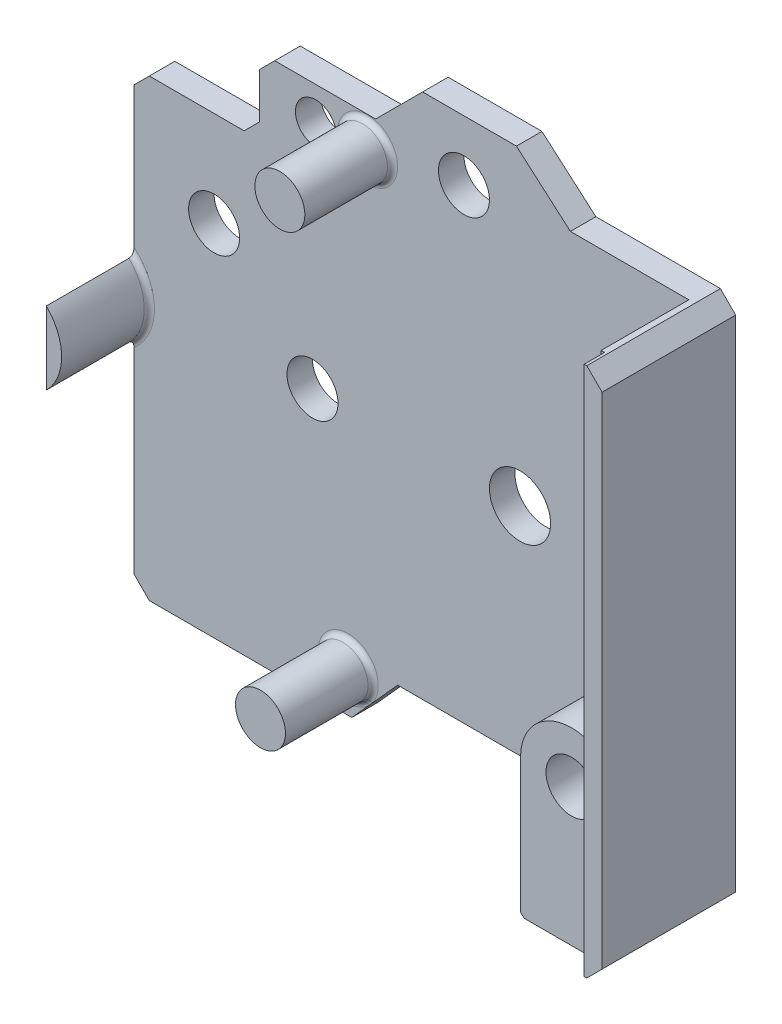
SolidWorks part; units mm, degrees
note: The reader was unsure of these and kept them because the rebuilt part matched: shared geometry of "스케치2<2>".
ref_plane "정면" through (0, 0, 0) normal (0, 0, 1) x (1, 0, 0)
ref_plane "윗면" through (0, 0, 0) normal (0, 1, 0) x (1, 0, 0)
ref_plane "우측면" through (0, 0, 0) normal (1, 0, 0) x (0, 0, -1)
sketch "스케치1" plane through (0, 0, 0) normal (0, 0, 1) x (1, 0, 0)
  line L0 (-6.6755, -27.7059) -> (-2.1735, -22.7059)
  line L1 (0.2695, 28.8941) -> (9.4695, 28.8941)
  line L2 (-42.0305, 9.3941) -> (-42.0305, -27.7059)
  line L3 (-42.0305, -27.7059) -> (-6.6755, -27.7059)
  line L4 (41.6695, 12.6741) -> (41.6695, -27.7059)
  line L5 (-2.1735, -22.7059) -> (13.2865, -22.7059)
  line L6 (13.2865, -22.7059) -> (18.8395, -27.7059)
  line L7 (18.8395, -27.7059) -> (41.6695, -27.7059)
  line L8 (-27.1305, 24.2941) -> (-42.0305, 9.3941)
  line L9 (30.0112, 24.2941) -> (41.6695, 12.6741)
  line L10 (0.2695, 28.8941) -> (-4.3305, 24.2941)
  line L11 (-4.3305, 24.2941) -> (-27.1305, 24.2941)
  line L12 (9.4695, 28.8941) -> (14.7612, 24.2941)
  line L13 (14.7612, 24.2941) -> (30.0112, 24.2941)
  line L14 (14.7612, 24.2941) -> (9.0921, 24.2941) construction
  circle A0 centre (-20.1788, 7.5041) radius 2.5
  circle A1 centre (4.3212, 23.0041) radius 2.5
  circle A2 centre (9.8212, -1.4959) radius 3
  point P0 (0, 0)
  dimension "D3" = 5
  dimension "D6" = 5
  dimension "D7" = 6
  dimension "D4" = 5
  dimension "D2" = 52
  dimension "D5" = 9
  dimension "D8" = 24.5
  dimension "D9" = 15.5
  dimension "D10" = 24.5
  dimension "D11" = 30
  dimension "D12" = 4.6
  dimension "D13" = 9.2
  dimension "D14" = 41
  dimension "D15" = 83.7
  dimension "D16" = 15.25
  dimension "D17" = 37.1
  dimension "D18" = 135
  dimension "D19" = 40.38
  dimension "D20" = 22.8
  dimension "D21" = 135
  dimension "D22" = 15.46
  dimension "D23" = 132
  dimension "D24" = 22.83
  dimension "D25" = 10.44
  dimension "D26" = 5.89
extrude "보스-돌출1" add sketch "스케치1" along normal blind 2.5
sketch "스케치2" plane through (0, 0, 2.5) normal (0, 0, 1) x (1, 0, 0)
  line L0 (-42.0305, 9.3941) -> (-42.0305, -27.7059) construction
  line L1 (-42.0305, -27.7059) -> (-6.6755, -27.7059) construction
  line L2 (41.6695, -27.7059) -> (41.6695, 12.6741) construction
  line L3 (18.8395, -27.7059) -> (41.6695, -27.7059) construction
  line L4 (-42.0305, -27.7059) -> (-6.6755, -27.7059) construction
  line L5 (-4.3305, 24.2941) -> (-27.1305, 24.2941) construction
  line L6 (-42.0305, 9.3941) -> (-42.0305, -27.7059) construction
  line L7 (18.4695, -14.2059) -> (18.4695, -27.3728)
  line L8 (13.2865, -22.7059) -> (18.8395, -27.7059) construction
  line L9 (18.4695, -27.3728) -> (18.8395, -27.7059)
  line L10 (18.8395, -27.7059) -> (28.4695, -27.7059)
  line L11 (28.4695, -27.7059) -> (28.4695, -14.2059)
  line L12 (-36.5305, -2.7059) -> (-36.5305, -27.7059)
  line L13 (28.4695, -14.2059) -> (28.4695, 24.2941)
  line L14 (-29.0305, -27.7059) -> (-36.5305, -27.7059)
  line L15 (-29.0305, -7.0361) -> (-29.0305, -27.7059)
  line L16 (30.0112, 24.2941) -> (14.7612, 24.2941) construction
  line L17 (28.4695, 24.2941) -> (26.3776, 24.2941)
  line L18 (26.3776, 24.2941) -> (26.3776, -10.1386)
  circle A0 centre (-31.5305, -2.7059) radius 2.5
  arc A2 (26.3776, -10.1386) -> (18.4695, -14.2059) centre (23.4695, -14.2059) ccw
  circle A3 centre (23.4695, -14.2059) radius 2.5
  circle A4 centre (-5.1305, 21.2941) radius 2.45
  circle A5 centre (-7.0305, -23.7059) radius 2.45
  arc A6 (-29.0305, -7.0361) -> (-36.5305, -2.7059) centre (-31.5305, -2.7059) ccw
  dimension "D2" = 5
  dimension "D5" = 10
  dimension "D6" = 5
  dimension "D9" = 4.9
  dimension "D12" = 4.9
  dimension "D3" = 10.5
  dimension "D4" = 25
  dimension "D7" = 18.2
  dimension "D8" = 13.5
  dimension "D10" = 3
  dimension "D11" = 22
  dimension "D13" = 4
  dimension "D14" = 35
  dimension "D15" = 55
  dimension "D16" = 11.5
  dimension "D17" = 26.4
  dimension "D18" = 24
extrude "보스-돌출3" add sketch "스케치2" along normal blind 8.6
extrude "컷-돌출1" cut sketch "스케치2<2>" against normal up to next contours A0 | A3
sketch "스케치2<2>" plane through (0, 0, 2.5) normal (0, 0, 1) x (1, 0, 0) same geometry as "스케치2"
fillet "필렛1" radius 0.5 7 edges at (21.1827, -9.7596, 2.5) (-7.5805, 21.2941, 2.5) (-9.4805, -23.7059, 2.5) (18.4695, -20.7894, 2.5) (-29.0305, 1.6242, 2.5)
sketch "스케치3" plane through (0, 0, 2.5) normal (0, 0, 1) x (1, 0, 0)
  line L0 (27.6311, 8.7556) -> (33.708, 8.7556)
  line L1 (34.708, 9.7556) -> (34.708, 15.8325)
  line L2 (33.708, 16.8325) -> (30.6695, 16.8325)
  line L3 (26.6311, 9.7556) -> (26.6311, 12.7941)
  line L4 (41.6695, -27.7059) -> (41.6695, 12.6741) construction
  line L6 (28.4695, -27.7059) -> (41.6695, -27.7059) construction
  arc A0 (30.6695, 16.8325) -> (26.6311, 12.7941) centre (30.6695, 12.7941) ccw
  arc A1 (27.6311, 8.7556) -> (26.6311, 9.7556) centre (27.6311, 9.7556) cw
  arc A2 (33.708, 8.7556) -> (34.708, 9.7556) centre (33.708, 9.7556) ccw
  arc A3 (34.708, 15.8325) -> (33.708, 16.8325) centre (33.708, 15.8325) ccw
  dimension "D3" = 1
  dimension "D1" = 11
  dimension "D2" = 40.5
  dimension "D4" = 8.0769
extrude "보스-돌출4" add sketch "스케치3" along normal blind 8.6 contours A0 L3 A1 L0 A2 L1 A3 L2
fillet "필렛4" radius 1 6 edges at (32.1888, 16.8325, 2.5) (34.708, 12.7941, 2.5) (31.0888, 8.7556, 2.5) (29.5223, 16.6662, 2.5) (34.4151, 16.5396, 2.5) (34.4151, 9.0485, 2.5)
chamfer "모따기1" distance 1 angle 45 2 edges at (41.6695, -27.7059, 1.25) (-42.0305, -27.7059, 1.25)
sketch "스케치6" plane through (0, 0, 11.1) normal (0, 0, 1) x (1, 0, 0)
  point P1 (30.6695, 12.7941)
  point P2 (23.4695, -14.2059)
sketch "스케치8" plane through (0, 0, 2.5) normal (0, 0, 1) x (1, 0, 0)
  line L0 (-15.7305, 24.2941) -> (-15.7305, 16.8441)
  line L1 (-4.3305, 24.2941) -> (-27.1305, 24.2941) construction
  line L2 (-15.7305, 16.8441) -> (-34.5805, 16.8441)
  line L3 (-27.1305, 24.2941) -> (-42.0305, 9.3941) construction
  line L4 (-34.5805, 16.8441) -> (-27.1305, 24.2941)
  line L5 (-27.1305, 24.2941) -> (-15.7305, 24.2941)
extrude "컷-돌출3" cut sketch "스케치8" against normal up to next and the other way through all
chamfer "모따기2" distance 1.5 angle 45 2 edges at (-15.7305, 24.2941, 1.25) (-15.7305, 16.8441, 1.25)
sketch "스케치10" plane through (0, 0, 2.5) normal (0, 0, 1) x (1, 0, 0)
  line L0 (41.6695, 12.6741) -> (30.0112, 24.2941) construction
  line L3 (35.708, 18.616) -> (35.708, -27.7059)
  line L5 (35.708, 18.616) -> (41.6695, 12.6741)
  line L6 (41.6695, 12.6741) -> (41.6695, -26.7059)
  line L7 (41.6695, -26.7059) -> (40.6695, -27.7059)
  line L8 (40.6695, -27.7059) -> (35.708, -27.7059)
  line L9 (-37.0305, -2.7059) -> (-37.0305, 14.3941)
  line L10 (28.4695, -27.7059) -> (40.6695, -27.7059) construction
  line L14 (-37.0305, 14.3941) -> (-42.0305, 9.3941)
  line L15 (-42.0305, 9.3941) -> (-42.0305, -26.7059)
  line L16 (-42.0305, -26.7059) -> (-41.0305, -27.7059)
  line L17 (-41.0305, -27.7059) -> (-37.0305, -27.7059)
  line L18 (-37.0305, -2.7059) -> (-37.0305, -27.7059)
  dimension "D1" = 5.5
  dimension "D2" = 5.0385
extrude "컷-돌출5" cut sketch "스케치10" against normal up to next
chamfer "모따기3" distance 2 angle 45 1 edges at (-37.0305, -27.7059, 1.25)
sketch "스케치11" plane through (0, -27.7059, 0) normal (0, -1, 0) x (1, 0, 0)
  line L0 (-36.5305, 11.1) -> (-29.0305, 3) construction
  line L2 (18.4695, 11.1) -> (28.4695, 3) construction
  point P12 (23.4695, 7.05)
  point P13 (-32.7805, 7.05)
hole_wizard "M5 나사 구멍2" positions "3D스케치2" profile "스케치13" tap size "M5" standard "KS"
sketch3d "3D스케치2"
  point P0 (23.4695, -27.7059, 7.05)
  point P4 (-32.7805, -27.7059, 7.05)
sketch "스케치13" plane through (23.4695, -27.7059, 7.05) normal (1, 0, 0) x (0, 0, -1)
  line L0 (0, 0) -> (0, 11.2618)
  line L1 (0, 11.2618) -> (2.1, 10)
  line L2 (2.1, 10) -> (2.1, 0)
  line L5 (2.1, 0) -> (0, 0)
  line L10 (0, 11.2618) -> (-2.1, 10) construction
  line L11 (0, -6.35) -> (0, 107.95) construction
  dimension "탭 드릴 지름" = 4.2
  dimension "탭 드릴 깊이" = 10
  dimension "드릴 각도" = 118
cosmetic thread "구멍 나사산1" parameters "D1"=8, "D2"=5
cosmetic thread "구멍 나사산2" parameters "D1"=8, "D2"=5
sketch "스케치14" plane through (0, 0, 2.5) normal (0, 0, 1) x (1, 0, 0)
  line L0 (-28.5305, -27.7059) -> (-6.6755, -27.7059) construction
  line L1 (-15.7305, 18.3441) -> (-15.7305, 22.7941) construction
  circle A0 centre (-10.5305, -1.7059) radius 2.5
  dimension "D1" = 5
  dimension "D2" = 26
  dimension "D3" = 5.2
extrude "컷-돌출6" cut sketch "스케치14" against normal up to next
sketch "스케치15" plane through (0, 0, 2.5) normal (0, 0, 1) x (1, 0, 0)
  line L1 (-28.0305, 16.8441) -> (-37.0305, 16.8441)
  line L2 (-28.0305, 16.8441) -> (-28.0305, -27.7059)
  line L3 (-28.0305, -27.7059) -> (-37.0305, -27.7059)
  line L4 (-37.0305, 16.8441) -> (-37.0305, -27.7059)
  line L5 (-37.0305, -2.7059) -> (-37.0305, 14.3941) construction
  line L6 (-28.5305, -27.7059) -> (-6.6755, -27.7059) construction
  line L7 (26.3776, 24.2941) -> (14.7612, 24.2941) construction
  line L8 (28.4695, -27.7059) -> (41.6695, -27.7059)
  line L9 (28.4695, -27.7059) -> (28.4695, 24.2941)
  line L10 (28.4695, 24.2941) -> (41.6695, 24.2941)
  line L11 (41.6695, -27.7059) -> (41.6695, 24.2941)
  line L12 (41.6695, -26.7059) -> (41.6695, 12.6741) construction
  dimension "D1" = 9
extrude "컷-돌출7" cut sketch "스케치15" against normal through all both and the other way through all
sketch "스케치17" plane through (26.3776, 0, 0) normal (-1, 0, 0) x (0, 0, 1)
  line L0 (2.5, 24.2941) -> (2.5, -9.5376) construction
  line L1 (11.1, 24.2941) -> (2.5, 24.2941) construction
  circle A0 centre (6.5, 13.2941) radius 2.5
  dimension "D1" = 5
  dimension "D2" = 4
  dimension "D3" = 11
extrude "보스-돌출5" add sketch "스케치17" along normal blind 3.5
fillet "필렛5" radius 2.4 1 edges at (22.8776, 13.2941, 9)
sketch "스케치18" plane through (0, 0, 11.1) normal (0, 0, 1) x (1, 0, 0)
  line L1 (26.7195, 24.2941) -> (28.4695, 24.2941)
  line L2 (26.7195, 24.2941) -> (26.7195, -27.7059)
  line L3 (26.7195, -27.7059) -> (28.4695, -27.7059)
  line L4 (28.4695, 24.2941) -> (28.4695, -27.7059)
  dimension "D1" = 1.75
extrude "보스-돌출6" add sketch "스케치18" along normal blind 2
chamfer "모따기4" distance 1.5 angle 45 4 edges at (-28.0305, -27.7059, 1.25) (-28.0305, 16.8441, 1.25) (28.4695, 24.2941, 6.55) (28.4695, -27.7059, 6.55)
sketch "스케치19" plane through (0, 0, 2.5) normal (0, 0, 1) x (1, 0, 0)
  line L0 (-15.7305, 18.3441) -> (-15.7305, 22.7941) construction
  line L1 (-4.3305, 24.2941) -> (-14.2305, 24.2941) construction
  circle A0 centre (-10.2005, 20.9941) radius 2
  dimension "D1" = 4
  dimension "D2" = 5.53
  dimension "D3" = 3.3
extrude "컷-돌출8" cut sketch "스케치19" against normal blind 10
